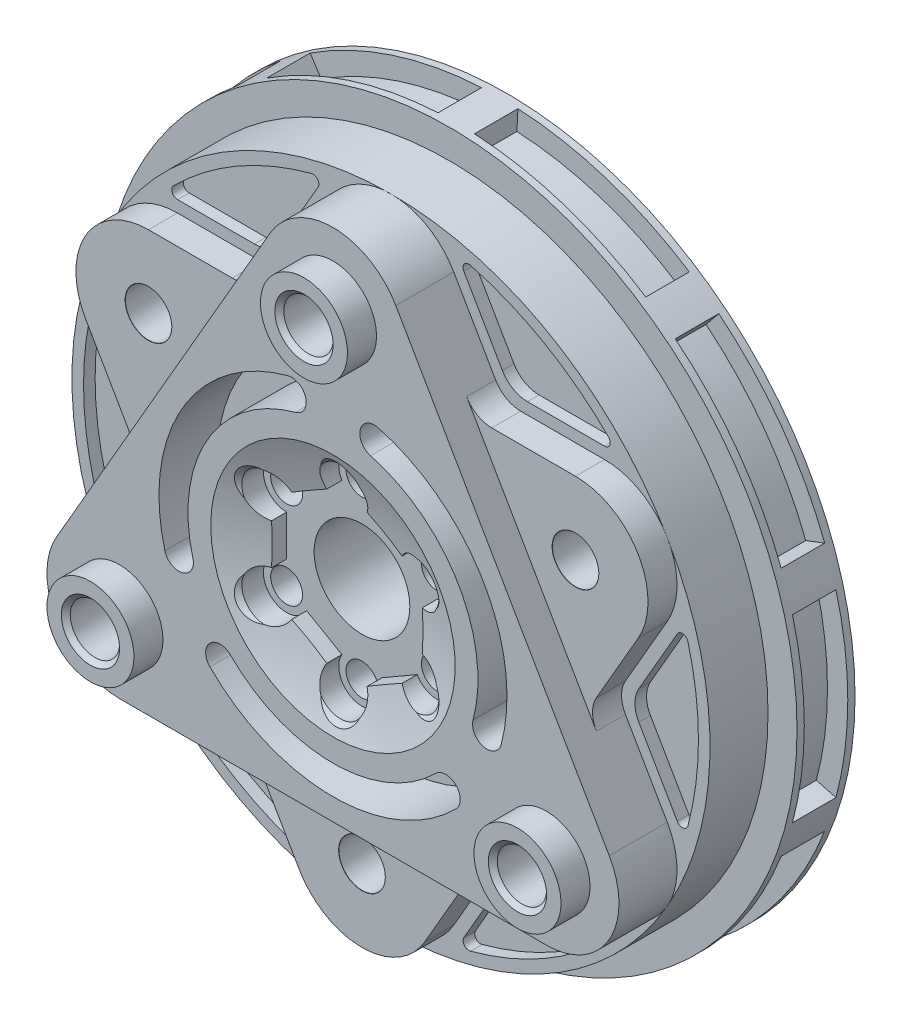
SolidWorks part; units mm, degrees
material "ASTM A36 Steel"
ref_plane "Front Plane" through (0, 0, 0) normal (0, 0, 1) x (1, 0, 0)
ref_plane "Top Plane" through (0, 0, 0) normal (0, 1, 0) x (1, 0, 0)
ref_plane "Right Plane" through (0, 0, 0) normal (1, 0, 0) x (0, 0, -1)
sketch "Sketch1" plane through (0, 0, 0) normal (0, 0, 1) x (1, 0, 0)
  line L1 (-10.8253, 48.75) -> (-47.6314, -15)
  line L2 (-36.8061, -33.75) -> (36.8061, -33.75)
  line L3 (47.6314, -15) -> (10.8253, 48.75)
  line L4 (36.8061, 33.75) -> (-36.8061, 33.75)
  line L5 (-47.6314, 15) -> (-10.8253, -48.75)
  line L6 (10.8253, -48.75) -> (47.6314, 15)
  circle A0 centre (0, 0) radius 60
  circle A1 centre (0, 0) radius 55
  circle A2 centre (0, 0) radius 33.75 construction
  arc A3 (-47.6314, -15) -> (-36.8061, -33.75) centre (-36.8061, -21.25) ccw
  arc A4 (-10.8253, 48.75) -> (10.8253, 48.75) centre (0, 42.5) cw
  arc A5 (36.8061, -33.75) -> (47.6314, -15) centre (36.8061, -21.25) ccw
  circle A6 centre (0, 0) radius 33.75 construction
  arc A7 (-10.8253, -48.75) -> (10.8253, -48.75) centre (0, -42.5) ccw
  arc A8 (36.8061, 33.75) -> (47.6314, 15) centre (36.8061, 21.25) cw
  arc A9 (-36.8061, 33.75) -> (-47.6314, 15) centre (-36.8061, 21.25) ccw
  dimension "D1" = 120
  dimension "D2" = 110
  dimension "D3" = 12.5
  dimension "D4" = 12.5
extrude "Boss-Extrude1" add sketch "Sketch1" along normal blind 10 contours A0
extrude "Boss-Extrude2" add sketch "Sketch1<3>" along normal blind 20 contours A1
sketch "Sketch1<3>" plane through (0, 0, 0) normal (0, 0, 1) x (1, 0, 0) same geometry as "Sketch1"
extrude "Boss-Extrude3" add sketch "Sketch1<4>" along normal blind 30 contours L1 A3 L2 A5 L3 A4
sketch "Sketch1<4>" plane through (0, 0, 0) normal (0, 0, 1) x (1, 0, 0) same geometry as "Sketch1"
extrude "Boss-Extrude4" add sketch "Sketch1<5>" along normal blind 5 from surface contours A8 L6 A7 L5 A9 L4 starting at face at (33.104, 19.1126, 20)
sketch "Sketch1<5>" plane through (0, 0, 0) normal (0, 0, 1) x (1, 0, 0) same geometry as "Sketch1"
sketch "Sketch2" plane through (0, 0, 30) normal (0, 0, 1) x (1, 0, 0)
  line L7 (0, 15) -> (-12.9904, 7.5)
  line L8 (-12.9904, 7.5) -> (-12.9904, -7.5)
  line L9 (-12.9904, -7.5) -> (0, -15)
  line L10 (0, -15) -> (12.9904, -7.5)
  line L11 (12.9904, -7.5) -> (12.9904, 7.5)
  line L12 (12.9904, 7.5) -> (0, 15)
  circle A0 centre (0, 0) radius 15 construction
  dimension "D1" = 30
extrude "Cut-Extrude1" cut sketch "Sketch2" against normal blind 5
sketch "Sketch3" plane through (0, 0, 25) normal (0, 0, 1) x (1, 0, 0)
  circle A0 centre (0, 0) radius 8.25
  dimension "D1" = 16.5
extrude "Cut-Extrude2" cut sketch "Sketch3" against normal through all
sketch "Sketch4" plane through (0, 0, 30) normal (0, 0, 1) x (1, 0, 0)
  point P0 (0, 15)
  point P3 (12.9904, 7.5)
  point P6 (12.9904, -7.5)
  point P9 (0, -15)
  point P12 (-12.9904, -7.5)
  point P15 (-12.9904, 7.5)
hole_wizard "CBORE for M5 SBHCS1" positions "Sketch4" profile "Sketch5" counterbore size "M5" standard "ANSI Metric" end condition through all
sketch "Sketch5" plane through (0, 15, 30) normal (1, 0, 0) x (0, -1, 0)
  line L0 (0, 0) -> (0, 30)
  line L1 (0, 30) -> (2.75, 30)
  line L3 (2.75, 30) -> (2.75, 5)
  line L4 (4, 5) -> (2.75, 5)
  line L5 (4, 5) -> (4, 1.275)
  line L6 (4, 1.275) -> (5.275, 0)
  line L7 (5.275, 0) -> (0, 0)
  line L8 (-4, 1.275) -> (-5.275, 0) construction
  line L11 (0, -6.35) -> (0, 107.95) construction
  dimension "Thru Hole Dia." = 5.5
  dimension "Thru Hole Depth" = 30
  dimension "C'Bore Dia." = 8
  dimension "C'Bore Depth" = 5
  dimension "Near C'Sink Dia." = 10.55
  dimension "Near C'Sink Angle" = 90
sketch "Sketch6" plane through (0, 0, 0) normal (1, 0, 0) x (0, 0, -1)
  line L0 (0, -60) -> (0, 60) construction
  line L1 (-54.5753, 49.6952) -> (-54.6363, -49.7307)
  line L2 (-83.5, 37.755) -> (-83.5, -37.755) construction
  arc A0 (-54.5753, 49.6952) -> (-54.6363, -49.7307) centre (-83.5, 0) cw
  point P9 (-83.5, 0)
  dimension "D1" = 57.5
  dimension "D2" = 83.5
revolve "Cut-Revolve1" cut sketch "Sketch6" angle 360 about L2
sketch "Sketch7" plane through (0, 0, 30) normal (0, 0, 1) x (1, 0, 0)
  circle A0 centre (0, 42.5) radius 7.5
  circle A1 centre (-36.8061, -21.25) radius 7.5
  circle A2 centre (36.8061, -21.25) radius 7.5
  dimension "D1" = 15
extrude "Boss-Extrude5" add sketch "Sketch7" along normal blind 5
sketch "Sketch8" plane through (0, 0, 35) normal (0, 0, 1) x (1, 0, 0)
  point P0 (-36.8061, -21.25)
  point P3 (0, 42.5)
  point P6 (36.8061, -21.25)
hole_wizard "M10x1.5 Tapped Hole1" positions "Sketch8" profile "Sketch9" tap size "M10x1.5" standard "ANSI Metric"
sketch "Sketch9" plane through (-36.8061, -21.25, 35) normal (1, 0, 0) x (0, -1, 0)
  line L0 (0, 0) -> (0, 25)
  line L1 (0, 25) -> (4.25, 22.4463)
  line L2 (4.25, 22.4463) -> (4.25, 0.775)
  line L3 (4.25, 0.775) -> (5.025, 0)
  line L5 (5.025, 0) -> (0, 0)
  line L6 (-4.25, 0.775) -> (-5.025, 0) construction
  line L10 (0, 25) -> (-4.25, 22.4463) construction
  line L11 (0, -6.35) -> (0, 107.95) construction
  dimension "Tap Drill Dia." = 8.5
  dimension "Tap Drill Depth" = 25
  dimension "Near C'Sink Dia." = 10.05
  dimension "Near C'Sink Angle" = 90
  dimension "Drill Angle" = 118
cosmetic thread "Hole Thread1" parameters "D1"=20, "D2"=10
cosmetic thread "Hole Thread2" parameters "D1"=20, "D2"=10
cosmetic thread "Hole Thread3" parameters "D1"=20, "D2"=10
sketch "Sketch10" plane through (0, 0, 30) normal (0, 0, 1) x (1, 0, 0)
  line L0 (0, 0) -> (87.6715, 0) construction
  line L1 (0, 0) -> (66.6409, 38.4752) construction
  arc A0 (7.1175, 26.563) -> (26.563, -7.1175) centre (0, 0) cw construction
  arc A1 (28.9778, -7.7646) -> (7.7646, 28.9778) centre (0, 0) ccw
  arc A2 (24.1481, -6.4705) -> (6.4705, 24.1481) centre (0, 0) ccw
  arc A3 (24.1481, -6.4705) -> (28.9778, -7.7646) centre (26.563, -7.1175) ccw
  arc A4 (7.7646, 28.9778) -> (6.4705, 24.1481) centre (7.1175, 26.563) ccw
  point P6 (23.8157, 13.75)
  point P11 (26.4129, -12.2701)
  dimension "D3" = 5
  dimension "D4" = 55
  dimension "D1" = 30
  dimension "D2" = 90
extrude "Cut-Extrude3" cut sketch "Sketch10" against normal blind 10
pattern_circular "CirPattern1" count 3 over 360 about axis through (0, 0, 30) along (0, 0, 1) of "Cut-Extrude3"
sketch "Sketch13" plane through (0, 0, 25) normal (0, 0, 1) x (1, 0, 0)
  point P0 (-36.8061, 21.25)
  point P3 (0, -42.5)
  point P6 (36.8061, 21.25)
hole_wizard "Ø8.0 (8) Diameter Hole2" positions "Sketch13" profile "Sketch14" hole size "Ø8.0" standard "ANSI Metric" end condition through all
sketch "Sketch14" plane through (-36.8061, 21.25, 25) normal (1, 0, 0) x (0, -1, 0)
  line L0 (0, 0) -> (0, 25)
  line L1 (0, 25) -> (4, 25)
  line L2 (4, 25) -> (4, 0.025)
  line L3 (4, 0.025) -> (4.025, 0)
  line L5 (4.025, 0) -> (0, 0)
  line L6 (-4, 0.025) -> (-4.025, 0) construction
  line L11 (0, -6.35) -> (0, 107.95) construction
  dimension "Thru Hole Dia." = 8
  dimension "Thru Hole Depth" = 25
  dimension "Near C'Sink Dia." = 8.05
  dimension "Near C'Sink Angle" = 90
sketch "Sketch15" plane through (0, 0, 20) normal (0, 0, 1) x (1, 0, 0)
  line L4 (-41.2805, 0) -> (-49.3634, 14)
  line L5 (-49.3634, -14) -> (-41.2805, 0)
  line L6 (-41.2805, 0) -> (-49.355, 13.9853)
  line L7 (-49.355, -13.9853) -> (-41.2805, 0)
  arc A3 (-49.355, -13.9853) -> (-51.1868, -13.7446) centre (-50.221, -13.4853) cw
  arc A4 (-51.1868, 13.7446) -> (-49.355, 13.9853) centre (-50.221, 13.4853) cw
  arc A6 (-50.433, 16.2945) -> (-49.3634, 14) centre (-36.8061, 21.25) ccw
  arc A7 (-50.433, 16.2945) -> (-50.433, -16.2945) centre (0, 0) ccw
  arc A8 (-49.3634, -14) -> (-50.433, -16.2945) centre (-36.8061, -21.25) ccw
  arc A9 (-50.433, 16.2945) -> (-49.3634, 14) centre (-36.8061, 21.25) ccw
  arc A10 (-51.1868, 13.7446) -> (-51.1868, -13.7446) centre (0, 0) ccw
  arc A11 (-49.3634, -14) -> (-50.433, -16.2945) centre (-36.8061, -21.25) ccw
  dimension "D2" = 1
  dimension "D1" = 2
extrude "Cut-Extrude4" cut sketch "Sketch15" against normal blind 2 contours A4 A10 A3 L7 L6 region at (-48.4961, 0, 20)
fillet "Fillet1" radius 5 1 edges at (-41.2805, 0, 19)
pattern_circular "CirPattern2" count 6 over 360 about axis through (0, 0, 20) along (0, 0, 1) of "Fillet1", "Cut-Extrude4"
fillet "Fillet2" radius 5 6 edges at (19.4856, -33.75, 22.5) (-19.4856, -33.75, 22.5) (-38.9711, 0, 22.5) (-19.4856, 33.75, 22.5) (38.9711, 0, 22.5) (19.4856, 33.75, 22.5)
ref_plane "Plane1" through (0, 0, 5) normal (0, 0, 1) x (1, 0, 0)
sketch "Sketch16" plane through (0, 0, 5) normal (0, 0, 1) x (1, 0, 0)
  line L0 (0, 0) -> (79.5164, 0) construction
  line L1 (54.5748, 14.6233) -> (57.9555, 15.5291)
  line L2 (54.5748, -14.6233) -> (57.9555, -15.5291)
  line L3 (54.5748, 14.6233) -> (0, 0) construction
  line L4 (0, 0) -> (54.5748, -14.6233) construction
  circle A2 centre (0, 0) radius 56.5
  arc A3 (54.5748, -14.6233) -> (54.5748, 14.6233) centre (0, 0) ccw
  circle A4 centre (0, 0) radius 60
  arc A5 (57.9555, -15.5291) -> (57.9555, 15.5291) centre (0, 0) ccw
  point P2 (58.6123, -15.5291)
  point P9 (58.7639, 15.5291)
  dimension "D2" = 30
  dimension "D1" = 3.5
  dimension "D3" = 0
extrude "Cut-Extrude7" cut sketch "Sketch16" against normal mid plane 7.5
pattern_circular "CirPattern3" count 10 over 360 about axis through (0, 0, 0) along (0, 0, 1) of "Cut-Extrude7"
